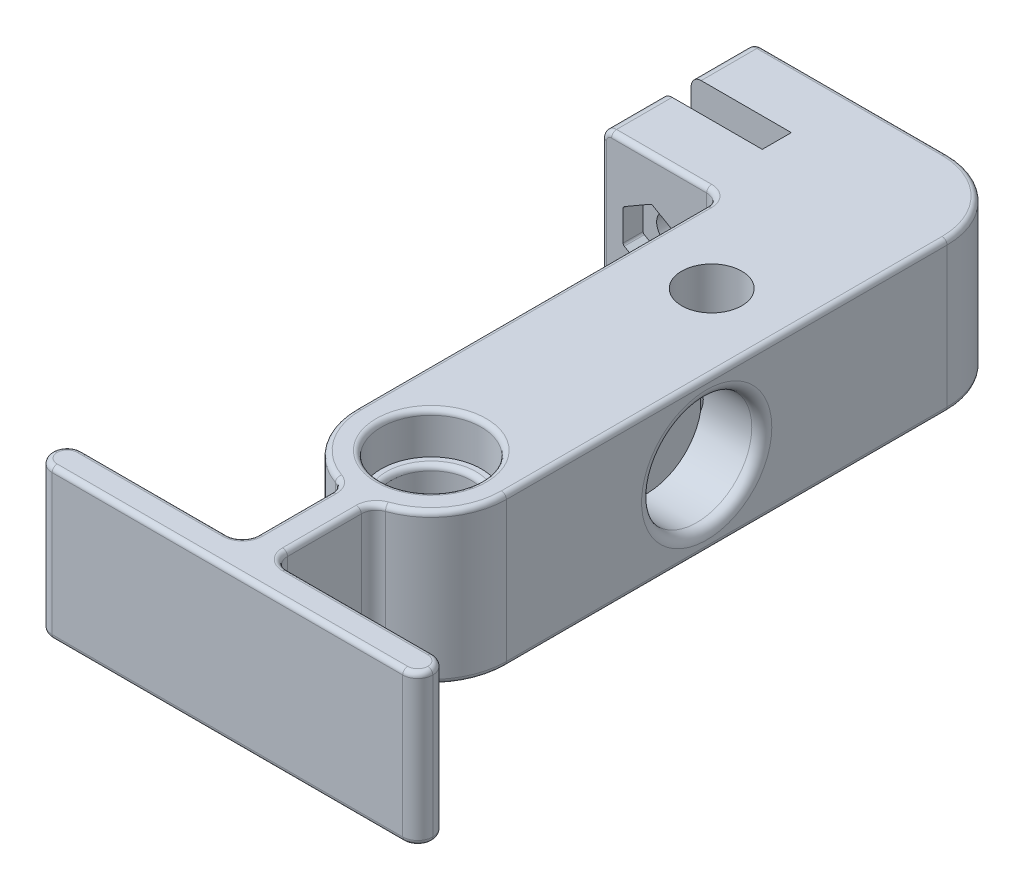
SolidWorks part; units mm, degrees
ref_plane "Front Plane" through (0, 0, 0) normal (0, 0, 1) x (1, 0, 0)
ref_plane "Top Plane" through (0, 0, 0) normal (0, 1, 0) x (1, 0, 0)
ref_plane "Right Plane" through (0, 0, 0) normal (1, 0, 0) x (0, 0, -1)
sketch "Sketch1" plane through (0, 0, 0) normal (0, 1, 0) x (1, 0, 0)
  line L0 (0, 22) -> (0, -22) construction
  line L1 (-7.5, 22) -> (7.5, 22)
  line L2 (-7.5, 22) -> (-7.5, -22)
  line L3 (-7.5, -22) -> (7.5, -22)
  line L4 (7.5, 22) -> (7.5, -22)
  line L5 (-7.5, 22) -> (7.5, -22) construction
  line L6 (-7.5, -22) -> (7.5, 22) construction
  circle A0 centre (0, -14.5) radius 4
  circle A1 centre (0, -14.5) radius 7.5
  point P0 (0, 0)
  dimension "D1" = 8
  dimension "D2" = 15
  dimension "D4" = 44
extrude "Boss-Extrude1" add sketch "Sketch1" along normal mid plane 15 contours L2 | L4 | A1 L4 L1 L2 | A1 A0 | L3 region at (0, 0, -6.6495) region at (0, 0, 7.2121)
sketch "Sketch2" plane through (0, 7.5, 0) normal (0, 1, 0) x (1, 0, 0)
  circle A0 centre (0, -14.5) radius 5
  dimension "D1" = 10
extrude "Cut-Extrude1" cut sketch "Sketch2" against normal blind 4.1
mirror "Mirror1" about plane through (0, 0, 0) normal (0, 1, 0) of "Cut-Extrude1"
sketch "Sketch12" plane through (0, -3.4, 0) normal (0, -1, 0) x (1, 0, 0)
  circle A0 centre (0, 14.5) radius 4 construction
  circle A1 centre (0, 14.5) radius 5
  circle A2 centre (0, 14.5) radius 5
  circle A3 centre (0, 14.5) radius 4
  dimension "D1" = 0
extrude "Cut-Extrude10" cut sketch "Sketch12" against normal blind 0.5
sketch "Sketch4" plane through (7.5, 0, 0) normal (1, 0, 0) x (0, 0, -1)
  line L0 (-3.1918, 0) -> (3.917, 0) construction
  line L2 (-9.5, 7.5) -> (-19.5, 7.5) construction
  line L3 (-9.5, 7.5) -> (-19.5, 7.5)
  line L4 (-14.5, 7.5) -> (-14.5, -7.5) construction
  line L5 (22, -7.5) -> (-14.5, -7.5) construction
  line L6 (5.5, 0) -> (5.5, 7.5) construction
  line L9 (22, 7.5) -> (-14.5, 7.5) construction
  circle A1 centre (5.5, 0) radius 5.5
  dimension "D1" = 20
  dimension "D2" = 11
extrude "Cut-Extrude3" cut sketch "Sketch4" against normal blind 6 contours A1 region at (7.5, 0, -5.5)
mirror "Mirror2" about plane through (0, 0, 0) normal (1, 0, 0) of "Cut-Extrude3"
sketch "Sketch18" plane through (0, -7.5, 0) normal (0, -1, 0) x (1, 0, 0)
  line L0 (0, -41.3409) -> (0, 22.3101) construction
  line L4 (7.5, -3.75) -> (-7.5, -3.75) construction
  line L5 (-19.5, -22) -> (-7.5, -22)
  line L6 (7.5, -29.5) -> (7.5, -22)
  line L7 (7.5, -22) -> (7.5, 14.5) construction
  line L8 (-7.5, -22) -> (7.5, -22)
  line L9 (-7.5, -22) -> (-7.5, 14.5) construction
  line L10 (0, -22) -> (0, -37) construction
  line L11 (0, -37) -> (-19.5, -37)
  line L13 (-19.5, -22) -> (-19.5, -37)
  circle A1 centre (0, -29.5) radius 7.5
  line M10 (-7.5, -22) -> (7.5, -22)
  dimension "D1" = 12
extrude "Boss-Extrude3" add sketch "Sketch18" against normal up to surface (15 mm away) contours A1 L6 L8 | A1 M10 | A1 | A1 L13 L11 region at (-12.5923, -7.5, -29.5) region at (5.8247, -7.5, -23.6753) region at (0, -7.5, -29.5) up to face at (0, 7.5, 19.5)
sketch "Sketch7" plane through (0, 7.5, 0) normal (0, 1, 0) x (1, 0, 0)
  line L0 (-19.5, 29.5) -> (7.5, 29.5) construction
  line L8 (7.5, 29.5) -> (7.5, -14.5) construction
  line L9 (-19.5, 28.05) -> (-9.5, 28.05)
  line L10 (-19.5, 28.05) -> (-19.5, 30.95)
  line L11 (-9.5, 28.05) -> (-9.5, 30.95)
  line L12 (-19.5, 30.95) -> (-9.5, 30.95)
  line L13 (-19.5, 28.05) -> (-9.5, 30.95) construction
  line L14 (-9.5, 28.05) -> (-19.5, 30.95) construction
  line L15 (-19.5, 22) -> (-19.5, 37) construction
  point P8 (-14.5, 29.5)
  dimension "D1" = 10
  dimension "D2" = 2.9
extrude "Cut-Extrude7" cut sketch "Sketch7" against normal up to next
sketch "Sketch8" plane through (-40.2452, 0, -37) normal (0, 0, 1) x (1, 0, 0)
  line L5 (20.7452, 0) -> (40.2452, 0) construction
  line L8 (20.7452, 7.5) -> (20.7452, -7.5) construction
  line L9 (40.2452, 7.5) -> (40.2452, -7.5) construction
  circle A2 centre (25.7452, 0) radius 1.5
  dimension "D2" = 5
  dimension "D3" = 3
extrude "Cut-Extrude8" cut sketch "Sketch8" along normal up to surface (15 mm away) contours A2
hole_wizard "CSK for M3 Flat Head Machine Screw1" positions "Sketch9" profile "Sketch10" countersink size "M3" standard "ANSI Metric"
sketch "Sketch9" plane through (-83.1458, 0, -37) normal (0, 0, 1) x (1, 0, 0)
  point P6 (68.6458, 0)
  point P17 (0, 0)
  point P18 (0, 0)
  point P19 (0, 0)
  point P20 (0, 0)
sketch "Sketch10" plane through (-14.5, 0, -37) normal (1, 0, 0) x (0, 1, 0)
  line L0 (0, 0) -> (0, 5.9013)
  line L1 (0, 5.9013) -> (1.5, 5)
  line L2 (1.5, 5) -> (1.5, 1.8)
  line L3 (1.5, 1.8) -> (3, 0.3)
  line L4 (3, 0.3) -> (3, 0)
  line L6 (3, 0) -> (0, 0)
  line L7 (-1.5, 1.8) -> (-3, 0.3) construction
  line L10 (0, 5.9013) -> (-1.5, 5) construction
  line L11 (0, -6.35) -> (0, 107.95) construction
  dimension "Hole Dia." = 3
  dimension "Hole Depth" = 5
  dimension "C'Sink Dia." = 6
  dimension "C'Sink Angle" = 90
  dimension "Drill Angle" = 118
  dimension "Head Clearance" = 0.3
sketch "Sketch11" plane through (15, 0, -22) normal (0, 0, 1) x (1, 0, 0)
  line L7 (-34.5, 7.5) -> (-34.5, -7.5) construction
  line L8 (-29.5, -3.2909) -> (-26.65, -1.6454)
  line L15 (-26.65, -1.6454) -> (-26.65, 1.6454)
  line L16 (-26.65, 1.6454) -> (-29.5, 3.2909)
  line L17 (-29.5, 3.2909) -> (-32.35, 1.6454)
  line L18 (-32.35, 1.6454) -> (-32.35, -1.6454)
  line L19 (-32.35, -1.6454) -> (-29.5, -3.2909)
  circle A0 centre (-29.5, 0) radius 2.85 construction
  dimension "D1" = 5.7
extrude "Cut-Extrude9" cut sketch "Sketch11" against normal blind 2
sketch "Sketch13" plane through (-44.6536, 0, -30.95) normal (0, 0, 1) x (1, 0, 0)
  line L0 (35.1536, -7.5) -> (35.1536, 7.5) construction
  line L2 (35.1536, -7.5) -> (35.1536, 7.5)
  line L3 (35.1536, 0) -> (44.6536, 0) construction
  line L4 (44.6536, 7.5) -> (44.6536, -7.5) construction
  line L5 (35.1536, 7.5) -> (42.6536, 0)
  line L6 (35.1536, -7.5) -> (42.6536, 0)
  dimension "D1" = 45
extrude "Cut-Extrude11" cut sketch "Sketch13" along normal up to surface (2.9 mm away) contours L5 L6 L2 up to face at (-13, 0, -28.05)
sketch "Sketch16" plane through (0, -7.5, 0) normal (0, -1, 0) x (1, 0, 0)
  line L0 (0, 42.718) -> (0, -5.4521) construction
  line L2 (-1.5, 31.8485) -> (1.5, 31.8485)
  line L3 (-1.5, 31.8485) -> (-1.5, 21.8485)
  line L4 (-1.5, 21.8485) -> (1.5, 21.8485)
  line L5 (1.5, 31.8485) -> (1.5, 21.8485)
  line L6 (-1.5, 31.8485) -> (1.5, 21.8485) construction
  line L7 (-1.5, 21.8485) -> (1.5, 31.8485) construction
  line L8 (-19, 34.8485) -> (19, 34.8485)
  line L9 (-19, 34.8485) -> (-19, 31.8485)
  line L10 (-19, 31.8485) -> (19, 31.8485)
  line L11 (19, 34.8485) -> (19, 31.8485)
  line L12 (-19, 34.8485) -> (19, 31.8485) construction
  line L13 (-19, 31.8485) -> (19, 34.8485) construction
  arc A0 (7.5, 14.5) -> (-7.5, 14.5) centre (0, 14.5) ccw construction
  point P1 (0, 26.8485)
  point P11 (0, 33.3485)
  arc M14 (7.5, 14.5) -> (-7.5, 14.5) centre (0, 14.5) ccw
  dimension "D1" = 3
  dimension "D2" = 10
  dimension "D3" = 38
extrude "Boss-Extrude2" add sketch "Sketch16" against normal up to surface (15 mm away) contours L5 L2 L3 M14 | L11 L8 L9 L10 L2 region at (0, -7.5, 33.3485) region at (0, -7.5, 26.899) up to face at (-8.677, 7.5, -20.9594)
sketch "Sketch19" plane through (0, -7.5, 0) normal (0, -1, 0) x (1, 0, 0)
  line L0 (0, 4.3088) -> (0, -5.4508) construction
  circle A0 centre (0, -13.5) radius 3
  circle A2 centre (0, 14.5) radius 5 construction
  dimension "D1" = 6
  dimension "D2" = 28
extrude "Cut-Extrude12" cut sketch "Sketch19" against normal up to next contours A0
fillet "Fillet12" radius 1.5 9 edges at (-1.5, 0, 31.8485) (-19, 0, 34.8485) (-19, 0, 31.8485) (-1.5, 0, 21.8485) (1.5, 0, 21.8485) (1.5, 0, 31.8485) (19, 0, 34.8485) (19, 0, 31.8485) (-7.5, 0, -22)
fillet "Fillet9" radius 1 6 edges at (-7.5, 0, -11) (7.5, 0, -11) (-19.5, 7.5, -25.025) (-19.5, -7.5, -25.025) (-19.5, -7.5, -33.975) (-19.5, 7.5, -33.975)
fillet "Fillet11" radius 0.25 6 edges at (-17.35, 1.6454, -23) (-17.35, -1.6454, -23) (-14.5, -3.2909, -23) (-11.65, -1.6454, -23) (-11.65, 1.6454, -23) (-14.5, 3.2909, -23)
fillet "Fillet10" radius 0.5 49 edges at (-7.5, -7.5, -3) (-6.1237, -7.5, 18.8301) (-1.5, -7.5, 26.6669) (0, -7.5, 34.8485) (1.5, -7.5, 26.6669) (6.1237, -7.5, 18.8301) (7.5, -7.5, -7.5) (5.3033, -7.5, -34.8033) (-9.25, -7.5, -37) (-19.5, 0, -37) (-9.25, 7.5, -37) (5.3033, 7.5, -34.8033) (7.5, 7.5, -7.5) (6.1237, 7.5, 18.8301) (1.5, 7.5, 26.6669) (0, 7.5, 34.8485) (-1.5, 7.5, 26.6669) (-6.1237, 7.5, 18.8301) (-7.5, 7.5, -3) (0, -7.5, 19.5) (0, 7.5, 19.5) (0, -2.9, 10.5) (0, 3.4, 18.5) (-1.7753, -7.5, 22.1193) (-1.9393, -7.5, 31.4091) (-10.25, -7.5, 31.8485) (-18.5607, -7.5, 32.2878) (-18.5607, -7.5, 34.4091) (18.5607, -7.5, 34.4091) (18.5607, -7.5, 32.2878) (10.25, -7.5, 31.8485) (1.9393, -7.5, 31.4091) (1.7753, -7.5, 22.1193) (-19.2071, -7.2071, -37) (-19.2071, 7.2071, -37) (1.7753, 7.5, 22.1193) (1.9393, 7.5, 31.4091) (10.25, 7.5, 31.8485) (18.5607, 7.5, 32.2878) (18.5607, 7.5, 34.4091) (-18.5607, 7.5, 34.4091) (-18.5607, 7.5, 32.2878) (-10.25, 7.5, 31.8485) (-1.9393, 7.5, 31.4091) (-1.7753, 7.5, 22.1193) (-7.9393, 7.5, -21.5607) (-13.75, 7.5, -22) (-19.2071, 7.2071, -22) (-7.9393, -7.5, -21.5607)
